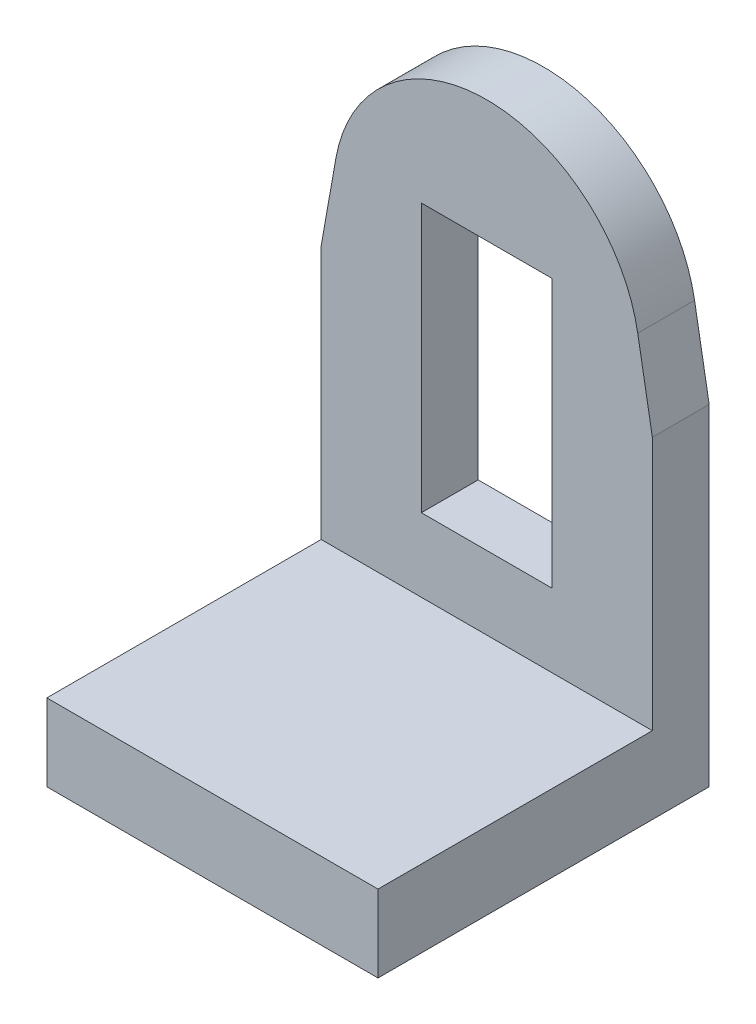
SolidWorks part; units mm, degrees
ref_plane "Front Plane" through (0, 0, 0) normal (0, 0, 1) x (1, 0, 0)
ref_plane "Top Plane" through (0, 0, 0) normal (0, 1, 0) x (1, 0, 0)
ref_plane "Right Plane" through (0, 0, 0) normal (1, 0, 0) x (0, 0, -1)
sketch "Sketch3" plane through (0, 0, 0) normal (0, 0, 1) x (1, 0, 0)
  line L0 (-31.9171, 0) -> (18.8829, 0)
  line L1 (55, 0) -> (-55, 0) construction
  line L2 (18.8829, 0) -> (18.8829, 50.8)
  line L3 (-31.9171, 0) -> (-31.9171, 50.8)
  line L4 (-31.9171, 50.8) -> (-29.6778, 63.5)
  line L5 (18.8829, 50.8) -> (16.6435, 63.5)
  arc A0 (-29.6778, 63.5) -> (16.6435, 63.5) centre (-6.5171, 59.4162) cw
  dimension "D3" = 59.4162
  dimension "D1" = 23.5179
  dimension "D2" = 170
  dimension "D4" = 50.8
  dimension "D5" = 170
extrude "Boss-Extrude2" add sketch "Sketch3" along normal blind 25.4 and the other way blind 25.4
sketch "Sketch4" plane through (0, 0, 0) normal (0, 1, 0) x (1, 0, 0)
  line L0 (-6.5171, 137.16) -> (-6.5171, -25.4) construction
  line L2 (-29.6778, -25.4) -> (16.6435, -25.4) construction
  line L3 (-31.9171, 0) -> (18.8829, 0) construction
  line L4 (-31.9171, 25.4) -> (-31.9171, -25.4) construction
  line L5 (18.8829, 25.4) -> (18.8829, -25.4) construction
  line L7 (-27.141, -33.2726) -> (14.1067, -33.2726)
  line L8 (-27.141, -33.2726) -> (-27.141, 33.2726)
  line L9 (-27.141, 33.2726) -> (14.1067, 33.2726)
  line L10 (14.1067, -33.2726) -> (14.1067, 33.2726)
  line L11 (-27.141, -33.2726) -> (14.1067, 33.2726) construction
  line L12 (-27.141, 33.2726) -> (14.1067, -33.2726) construction
  point P3 (-6.5171, 55.88)
  point P11 (-6.5171, 0)
ref_plane "Plane1" through (0, 82.9341, 0) normal (0, 1, 0) x (1, 0, 0)
sketch "Sketch5" plane through (0, 82.9341, 0) normal (0, 1, 0) x (1, 0, 0)
  line L6 (-35.0287, -26.359) -> (20.9673, -26.359)
  line L8 (-35.0287, -26.359) -> (-35.0287, 16.6825)
  line L9 (-35.0287, 16.6825) -> (20.9673, 16.6825)
  line L10 (20.9673, -26.359) -> (20.9673, 16.6825)
extrude "Cut-Extrude2" cut sketch "Sketch5" against normal blind 71.12
sketch "Sketch8" plane through (0, 0, 25.4) normal (0, 0, 1) x (1, 0, 0)
  line L4 (-6.5171, 82.9341) -> (-6.5171, 11.8141) construction
  line L5 (18.8829, 11.8141) -> (-31.9171, 11.8141) construction
  line L7 (-16.5501, 23.0518) -> (3.5159, 23.0518)
  line L8 (-16.5501, 23.0518) -> (-16.5501, 64.1998)
  line L9 (-16.5501, 64.1998) -> (3.5159, 64.1998)
  line L10 (3.5159, 23.0518) -> (3.5159, 64.1998)
  line L11 (-16.5501, 23.0518) -> (3.5159, 64.1998) construction
  line L12 (-16.5501, 64.1998) -> (3.5159, 23.0518) construction
  arc A0 (16.6435, 63.5) -> (-29.6778, 63.5) centre (-6.5171, 59.4162) ccw construction
  point P9 (-6.5171, 43.6258)
  dimension "D1" = 20.066
  dimension "D2" = 41.148
extrude "Cut-Extrude4" cut sketch "Sketch8" against normal up to next
